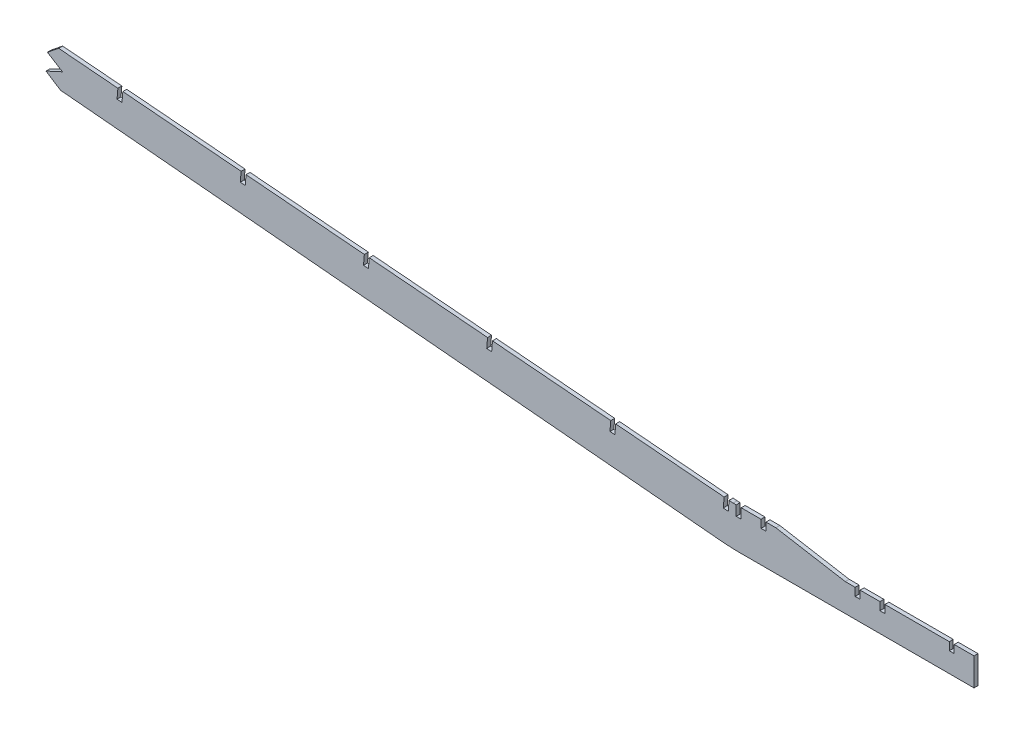
SolidWorks part; units mm, degrees
ref_plane "Front Plane" through (0, 0, 0) normal (0, 0, 1) x (1, 0, 0)
ref_plane "Top Plane" through (0, 0, 0) normal (0, 1, 0) x (1, 0, 0)
ref_plane "Right Plane" through (0, 0, 0) normal (1, 0, 0) x (0, 0, -1)
sketch "Sketch1" plane through (0, 0, 0) normal (0, 0, 1) x (1, 0, 0)
  line L0 (-949.6524, 80.0757) -> (-9.8872, -5.2596)
  line L1 (-945.9572, 86.1378) -> (-949.6524, 80.0757)
  line L8 (-6.7234, -5.5253) -> (-5.1293, 13.4579)
  line L9 (-5.1293, 13.4579) -> (-8.2932, 13.7235)
  line L10 (-8.2932, 13.7235) -> (-9.8872, -5.2596)
  line L11 (-9.8872, -5.2596) -> (-6.7234, -5.5253)
  line L12 (3.175, -5.8337) -> (3.175, 13.2163)
  line L13 (3.175, 13.2163) -> (0, 13.2163)
  line L14 (0, 13.2163) -> (0, -5.8337)
  line L15 (0, -5.8337) -> (3.175, -5.8337)
  line L17 (-943.1142, 119.9943) -> (-945.9572, 86.1378)
  line L18 (-945.9572, 86.1378) -> (-9.8872, -5.2596)
  line L19 (-6.7234, -5.5253) -> (0, -5.8337)
  line L20 (3.175, -5.8337) -> (152.4, -5.8337)
  line L21 (152.4, -5.8337) -> (152.4, 11.9463)
  line L22 (152.4, 11.9463) -> (69.85, 11.9463)
  line L23 (69.85, 11.9463) -> (25.4, 19.5663)
  line L24 (25.4, 19.5663) -> (-1.9861, 19.5663)
  line L25 (-1.9861, 19.5663) -> (-944.8986, 98.7448)
  line L26 (0, 13.2163) -> (0, 19.5663)
  line L27 (3.175, 13.2163) -> (3.175, 19.5663)
  line L28 (-5.1293, 13.4579) -> (-4.598, 19.7856)
  line L29 (-8.2932, 13.7235) -> (-7.7618, 20.0513)
  line L30 (-8.2932, 13.7235) -> (-945.4292, 92.426)
  line L31 (15.875, 19.5663) -> (15.875, 14.4863)
  line L32 (15.875, 14.4863) -> (19.05, 14.4863)
  line L33 (19.05, 14.4863) -> (19.05, 19.5663)
  line L34 (76.2, 6.8663) -> (76.2, 11.9463)
  line L35 (76.2, 6.8663) -> (79.375, 6.8663)
  line L36 (79.375, 6.8663) -> (79.375, 11.9463)
  line L37 (92.075, 11.9463) -> (92.075, 6.8663)
  line L38 (92.075, 6.8663) -> (95.25, 6.8663)
  line L39 (95.25, 6.8663) -> (95.25, 11.9463)
  line L40 (136.525, 11.9463) -> (136.525, 6.8663)
  line L41 (136.525, 6.8663) -> (139.7, 6.8663)
  line L42 (139.7, 6.8663) -> (139.7, 11.9463)
  line L44 (-949.6524, 80.0757) -> (-949.1211, 86.4035)
  line L45 (-949.1211, 86.4035) -> (-945.959, 86.1163)
  dimension "D1" = 25.4
  dimension "D2" = 6.35
extrude "Boss-Extrude1" add sketch "Sketch1" along normal blind 2.54 contours L42 L41 L40 L22 L39 L38 L37 L36 L35 L34 L23 L24 L33 L32 L31 L27 L12 L20 L21 | L30 L29 L25 L17 | L28 L8 L19 L14 L26 L24 L25 | L10 L11 L8 L9 | L14 L15 L12 L13 | L45 L44 L17 | L10 L30 L17 L18 | L18 L1 L0 region at (-635.1656, 53.6513, 0) region at (-948.2478, 84.1988, 0) region at (-398.9758, 39.6362, 0) region at (-7.5083, 4.0991, 0) region at (-476.4854, 56.2272, 0) region at (-2.8648, 6.1846, 0) region at (1.5875, 3.6913, 0) region at (71.853, 4.2703, 0)
sketch "Sketch2" plane through (0, 0, 2.54) normal (0, 0, 1) x (1, 0, 0)
  line L1 (-76.483, 72.8473) -> (-82.5095, 1.0799)
  line L3 (-155.6446, 77.1971) -> (-161.4339, 8.255)
  line L5 (-234.8005, 81.6162) -> (-240.3617, 15.3891)
  line L7 (-313.9625, 85.9617) -> (-319.2865, 22.5591)
  line L9 (-393.1191, 90.3714) -> (-398.2146, 29.6908)
  line L11 (-472.2837, 94.686) -> (-477.1388, 36.8682)
  line L13 (-551.4418, 99.0783) -> (-556.0668, 44.0001)
  line L15 (-630.6082, 103.3716) -> (-634.991, 51.1773)
  line L17 (-709.7674, 107.7507) -> (-713.9195, 58.3043)
  line L19 (-788.9364, 112.0121) -> (-792.8436, 65.483)
  line L21 (-868.0976, 116.3681) -> (-871.7723, 72.6069)
  line L23 (-73.3191, 72.5816) -> (-79.3456, 0.8143)
  line L25 (-152.4808, 76.9314) -> (-158.27, 7.9893)
  line L27 (-231.6366, 81.3506) -> (-237.1978, 15.1234)
  line L29 (-310.7986, 85.696) -> (-316.1227, 22.2934)
  line L31 (-389.9552, 90.1057) -> (-395.0507, 29.4251)
  line L33 (-469.1198, 94.4203) -> (-473.9749, 36.6025)
  line L35 (-548.2779, 98.8126) -> (-552.903, 43.7344)
  line L37 (-627.4443, 103.1059) -> (-631.8272, 50.9116)
  line L39 (-706.6035, 107.485) -> (-710.7556, 58.0386)
  line L41 (-785.7726, 111.7464) -> (-789.6797, 65.2173)
  line L43 (-864.9337, 116.1024) -> (-868.6084, 72.3413)
  line L45 (-8.2932, 13.7235) -> (-945.4292, 92.426)
  line L47 (-7.7618, 20.0513) -> (-944.8986, 98.7448)
  line M27 (-7.7618, 20.0513) -> (-944.8986, 98.7448)
extrude "Cut-Extrude1" cut sketch "Sketch2" against normal through all and the other way through all contours L45 L43 L21 M27 | L45 L41 L19 M27 | L45 L39 L17 M27 | L45 L37 L15 M27 | L45 L35 L13 M27 | L45 L33 L11 M27 | L45 L31 L9 M27 | L45 L29 L7 M27 | L45 L27 L5 M27 | L45 L25 L3 M27 | L45 L23 L1 M27 region at (-79.0879, 22.8549, 2.54) region at (-158.0579, 29.4865, 2.54) region at (-237.0279, 36.1182, 2.54) region at (-315.998, 42.7499, 2.54) region at (-394.968, 49.3816, 2.54) region at (-473.938, 56.0132, 2.54) region at (-552.9081, 62.6449, 2.54) region at (-631.8781, 69.2766, 2.54) region at (-710.8481, 75.9083, 2.54) region at (-789.8182, 82.54, 2.54) region at (-868.7882, 89.1716, 2.54)
sketch "Sketch3" plane through (0, 0, 2.54) normal (0, 0, 1) x (1, 0, 0)
  line L0 (-434.1875, 55.8592) -> (-441.4445, 50.0741)
  line L1 (-396.2844, 52.6764) -> (-472.0906, 59.042) construction
  line L2 (-441.4445, 50.0741) -> (-431.803, 44.0226)
  line L3 (-431.803, 44.0226) -> (-442.3497, 39.1715)
  line L4 (-442.3497, 39.1715) -> (-433.0143, 33.1624)
  line L5 (-949.6524, 80.0757) -> (-9.8872, -5.2596) construction
  line L6 (-434.1875, 55.8592) -> (-979.2227, 133.8808)
  line L7 (-979.2227, 133.8808) -> (-1000.0741, -11.7803)
  line L8 (-1000.0741, -11.7803) -> (-433.0143, 33.1624)
extrude "Cut-Extrude2" cut sketch "Sketch3" against normal blind 7.62 contours L8 L4 L3 L2 L0 L6 L7
